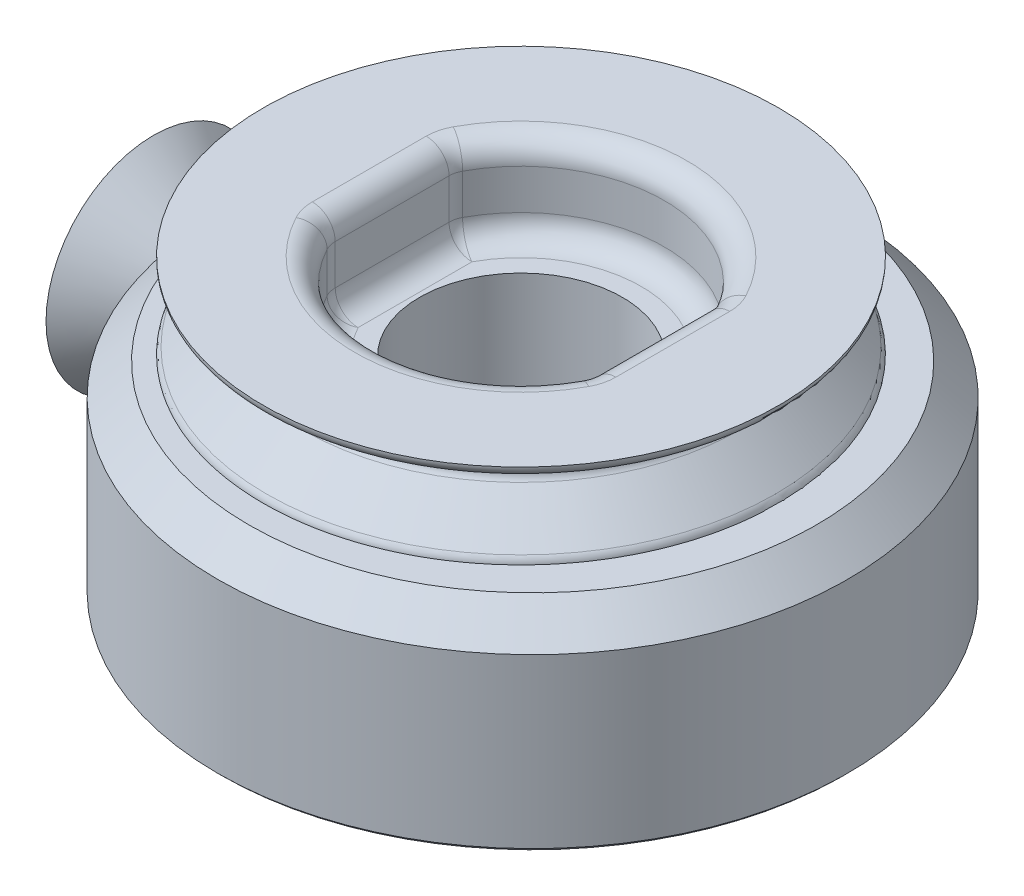
SolidWorks part; units mm, degrees
material "AISI 1020 Steel, Cold Rolled"
ref_plane "Front Plane" through (0, 0, 0) normal (0, 0, 1) x (1, 0, 0)
ref_plane "Top Plane" through (0, 0, 0) normal (0, 1, 0) x (1, 0, 0)
ref_plane "Right Plane" through (0, 0, 0) normal (1, 0, 0) x (0, 0, -1)
other "Center of Mass"
sketch "Sketch1" plane through (0, 0, 0) normal (0, 1, 0) x (1, 0, 0)
  circle A0 centre (0, 0) radius 34.925
  circle A1 centre (0, 0) radius 23.8125
  dimension "D1" = 69.85
  dimension "D2" = 47.625
extrude "Boss-Extrude1" add sketch "Sketch1" along normal mid plane 22.479
chamfer "Chamfer1" distance 2.159 angle 45 2 edges at (0, -11.2395, 23.8125) (0, 11.2395, 23.8125)
chamfer "Chamfer2" distance 3.4798 angle 45 1 edges at (0, 11.2395, 34.925)
chamfer "Chamfer3" distance 0.381 angle 45 1 edges at (0, -11.2395, 34.925)
sketch "Sketch2" plane through (0, 0, 0) normal (0, 1, 0) x (1, 0, 0)
  line L0 (-42.037, 11.9126) -> (-42.037, 0)
  line L1 (-42.037, 0) -> (-17.1196, 0)
  line L2 (-17.1196, 0) -> (-17.1196, 5.3693)
  line L3 (-17.1196, 5.3693) -> (-34.5098, 5.3693)
  line L4 (-34.5098, 5.3693) -> (-42.037, 11.9126)
  circle A0 centre (0, 0) radius 34.925 construction
  point P7 (34.925, 0)
  dimension "D1" = 24.9174
  dimension "D2" = 76.962
  dimension "D3" = 41
  dimension "D4" = 11.9126
revolve "Revolve1" add sketch "Sketch2" angle 360 about L1
other "Center of Mass Reference Point1"
chamfer "Chamfer4" distance 1.27 angle 45 1 edges at (-17.1196, 0, 5.3693)
sketch "Sketch3" plane through (0, 0, 0) normal (0, 1, 0) x (1, 0, 0)
  line L0 (-22.9502, 6.35) -> (-16.4502, 6.35)
  line L1 (-16.4502, 6.35) -> (-16.4502, -6.35)
  line L2 (-16.4502, -6.35) -> (-22.9502, -6.35)
  arc A0 (-22.9502, -6.35) -> (-22.9502, 6.35) centre (0, 0) ccw
  circle A1 centre (0, 0) radius 23.8125 construction
  dimension "D1" = 12.7
  dimension "D2" = 6.5
extrude "Boss-Extrude2" add sketch "Sketch3" along normal mid plane 22.225 separate body
sketch "Sketch4" plane through (0, 11.1125, 0) normal (0, 1, 0) x (1, 0, 0)
  circle A0 centre (-1.2893, 0) radius 11.25
  dimension "D1" = 22.5
  dimension "D2" = 1.2893
extrude "Cut-Extrude1" cut sketch "Sketch4" against normal through all both and the other way through all
ref_axis "Axis1" through (-1.2893, -11.1125, 0) along (0, 1, 0)
fillet "Fillet1" radius 3.302 2 edges at (-16.4502, 0, 6.35) (-16.4502, 0, -6.35)
sketch "Sketch6" plane through (-42.037, 0, 0) normal (-1, 0, 0) x (0, 0, 1)
  line L1 (-4.6194, 0) -> (-2.3097, -4.0005)
  line L2 (-2.3097, -4.0005) -> (2.3097, -4.0005)
  line L3 (2.3097, -4.0005) -> (4.6194, 0)
  line L4 (4.6194, 0) -> (2.3097, 4.0005)
  line L5 (2.3097, 4.0005) -> (-2.3097, 4.0005)
  line L6 (-2.3097, 4.0005) -> (-4.6194, 0)
  circle A0 centre (0, 0) radius 4.0005 construction
  dimension "D1" = 8.001
extrude "Cut-Extrude3" cut sketch "Sketch6" against normal blind 6.35
sketch "Sketch7" plane through (0, 11.1125, 0) normal (0, 1, 0) x (1, 0, 0)
  line L0 (-15.5768, 6.9198) -> (-15.5768, -6.9198)
  line L1 (12.9982, 6.9198) -> (12.9982, -6.9198)
  circle A0 centre (-1.2893, 0) radius 28.575
  arc A1 (12.9982, 6.9198) -> (-15.5768, 6.9198) centre (-1.2893, 0) ccw
  arc A2 (-15.5768, -6.9198) -> (12.9982, -6.9198) centre (-1.2893, 0) ccw
  dimension "D1" = 57.15
  dimension "D2" = 31.75
  dimension "D3" = 28.575
extrude "Boss-Extrude3" add sketch "Sketch7" along normal blind 9.525
fillet "Fillet2" radius 2.54 12 edges at (12.9982, 20.6375, 0) (12.9982, 11.1125, 0) (12.9982, 15.875, 6.9198) (-1.2893, 20.6375, 15.875) (-1.2893, 11.1125, 15.875) (-15.5768, 15.875, 6.9198) (-15.5768, 20.6375, 0) (-15.5768, 11.1125, 0) (-15.5768, 15.875, -6.9198) (-1.2893, 20.6375, -15.875) (12.9982, 15.875, -6.9198) (-1.2893, 11.1125, -15.875)
sketch "Sketch9" plane through (0, 0, 0) normal (0, 0, 1) x (1, 0, 0)
  line L0 (-49.1154, 15.3453) -> (-37.1526, 15.3453) construction
  line L1 (-37.1526, 15.3453) -> (-37.1526, 18.5203) construction
  line L2 (-37.1526, 18.5203) -> (-52.7445, 18.5203) construction
  line L3 (-29.8643, 20.6375) -> (-29.8643, 11.1125)
  line L4 (-29.1426, 19.537) -> (-25.8309, 18.0975)
  line L5 (-25.4391, 16.0347) -> (-29.5128, 11.961)
  line L7 (-37.1526, 16.9328) -> (-26.3371, 16.9328) construction
  line L8 (27.2857, 20.6375) -> (-29.8643, 20.6375) construction
  line L9 (-1.2893, 9.7331) -> (-1.2893, 23.545) construction
  line L10 (-1.2893, -11.1125) -> (-1.2893, 11.1125) construction
  arc A0 (-29.8643, 20.6375) -> (-29.1426, 19.537) centre (-28.6643, 20.6375) ccw
  arc A1 (-25.8309, 18.0975) -> (-25.4391, 16.0347) centre (-26.3371, 16.9328) cw
  arc A2 (-29.5128, 11.961) -> (-29.8643, 11.1125) centre (-28.6643, 11.1125) ccw
  dimension "D2" = 1.27
  dimension "D4" = 1.2
  dimension "D1" = 3.175
  dimension "D3" = 45
  dimension "D5" = 2.54
revolve "Cut-Revolve1" cut sketch "Sketch9" angle 360 about L9
fillet "Fillet3" radius 0.8 2 edges at (-22.9502, 0, -6.35) (-22.9502, 0, 6.35)
ref_plane "Plane1" through (0, 4.699, 0) normal (0, 1, 0) x (1, 0, 0)
